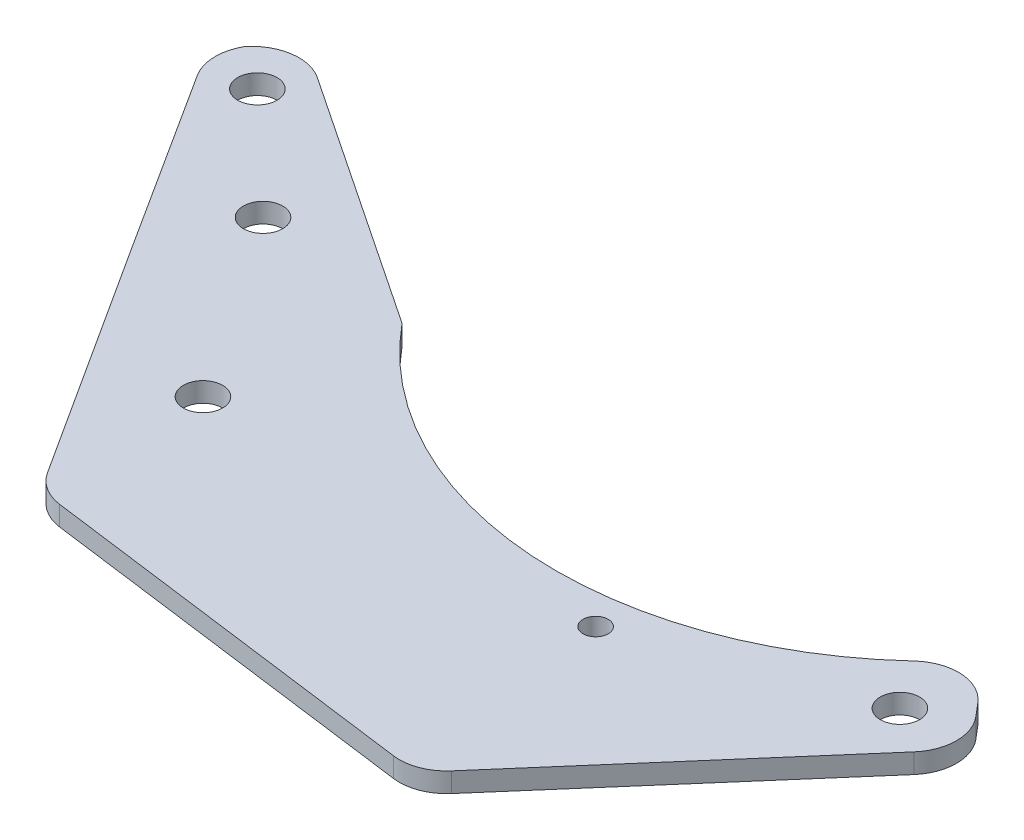
SolidWorks part; units mm, degrees
ref_plane "Front Plane" through (0, 0, 0) normal (0, 0, 1) x (1, 0, 0)
ref_plane "Top Plane" through (0, 0, 0) normal (0, 1, 0) x (1, 0, 0)
ref_plane "Right Plane" through (0, 0, 0) normal (1, 0, 0) x (0, 0, -1)
sketch "Sketch1" plane through (0, 0, 0) normal (0, 1, 0) x (1, 0, 0)
  line L0 (94.0778, -14.7948) -> (105.5911, -28.3436)
  line L2 (-5.7083, -67.1691) -> (-31.7828, -26.689)
  line L3 (-31.7828, -26.689) -> (0.0978, -14.6991)
  line L4 (-5.7083, -67.1691) -> (63.9398, -76.3764)
  line L5 (63.9398, -76.3764) -> (105.5911, -28.3436)
  line L6 (-5.7083, -67.1691) -> (-31.7828, -26.689)
  line L7 (0.0978, -14.6991) -> (-31.7828, -26.689)
  line L8 (0.0978, -14.6991) -> (-47.4406, 17.0522)
  line L9 (-31.7828, -26.689) -> (-53.7452, 7.6128)
  line L10 (-47.4406, 17.0522) -> (-53.7452, 7.6128)
  line L11 (-50.5929, 12.3325) -> (-15.8425, -20.694) construction
  line L12 (-5.7083, -67.1691) -> (63.9398, -76.3764)
  line L13 (63.9398, -76.3764) -> (57.1891, -36.0371)
  arc A0 (0.0978, -14.6991) -> (94.0778, -14.7948) centre (47.1273, 24.0868) ccw
  circle A1 centre (-25.9198, -11.1166) radius 3.175
  circle A2 centre (94.0778, -28.3436) radius 3.175
  circle A3 centre (-5.7083, -41.0206) radius 3.175
  circle A4 centre (58.0979, -41.4677) radius 2.032
  circle A5 centre (-44.3312, 6.3814) radius 3.175
  point P4 (0, 0)
  point P21 (0, 0)
  point P24 (-34.9599, 9.9655)
  point P25 (-19.2693, 22.8791)
  point P26 (-18.7402, 22.2509)
  point P27 (0, 0)
  point P28 (0, 0)
  point P29 (0, 0)
  point P30 (-61.053, 12.3752)
  point P31 (-64.9943, -2.1583)
  point P32 (-34.3672, 22.8032)
  point P33 (-53.7452, 7.6128)
  point P34 (0, 0)
  point P35 (0, 0)
  point P36 (0, 0)
  point P37 (-40.7514, 13.4274)
  point P38 (-40.7514, 13.0007)
  point P39 (0.0978, -13.3062)
  point P40 (-15.4443, -2.0311)
  point P41 (0, 0)
  point P42 (-15.4403, -13.3062)
  point P43 (-15.4403, -13.3062)
  point P44 (-15.4374, -13.2833)
  point P45 (-33.7755, -28.3436)
  point P46 (-3.4295, -44.5718)
  point P47 (0.0978, -59.4886)
  point P48 (-21.5982, -7.8093)
  point P49 (0, 0)
  point P50 (0, 0)
  point P51 (0, 0)
  point P52 (0, -8.1069)
  point P53 (-45.417, 9.8545)
  point P54 (-37.3398, 2.1697)
  point P55 (-38.3506, 4.2756)
  point P56 (46.663, -43.1112)
  point P57 (46.663, -66.1494)
  point P58 (60.5243, -72.0698)
  point P59 (-5.7083, -67.1691)
  point P60 (63.9398, -76.3764)
  point P61 (0, 0)
  dimension "D7" = 6.35
  dimension "D6" = 60.96
  dimension "D8" = 4.064
  dimension "D1" = 17.78
  dimension "D2" = 93.98
  dimension "D3" = 25.4
extrude "Boss-Extrude1" add sketch "Sketch1" along normal blind 3.175 contours L3 A0 L0 L5 L4 L2 | A3 | A4 | A1 | A2 | L7 L8 L10 L9 | A5
fillet "Fillet1" radius 7.62 7 edges at (94.0778, 1.5875, 14.7948) (105.5911, 1.5875, 28.3436) (63.9398, 1.5875, 76.3764) (-5.7083, 1.5875, 67.1691) (-31.7828, 1.5875, 26.689) (-47.4406, 1.5875, -17.0522) (-53.7452, 1.5875, -7.6128)
